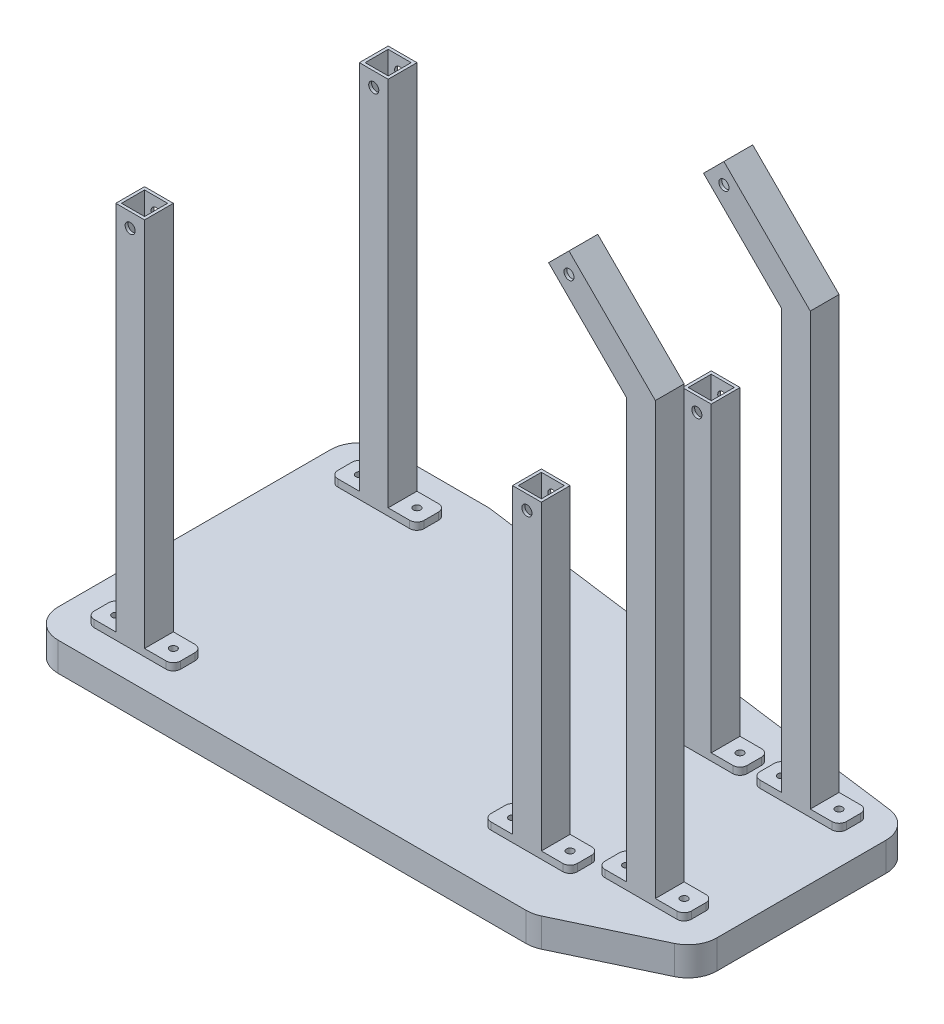
SolidWorks part; units mm, degrees
note: The reader was unsure of these and kept them because the rebuilt part matched: shared geometry of "Sketch4<3>".
ref_plane "Front Plane" through (0, 0, 0) normal (0, 0, 1) x (1, 0, 0)
ref_plane "Top Plane" through (0, 0, 0) normal (0, 1, 0) x (1, 0, 0)
ref_plane "Right Plane" through (0, 0, 0) normal (1, 0, 0) x (0, 0, -1)
sketch "Sketch3" plane through (0, 0, 0) normal (0, 0, 1) x (1, 0, 0)
  line L1 (-396.8516, 25.4) -> (358.309, 25.4) construction
  line L2 (-358.4449, 31.75) -> (285.9975, 31.75) construction
  circle A0 centre (0, 285.496) radius 4.445
  circle A2 centre (23.114, 470.408) radius 4.445
  circle A3 centre (-329.692, 346.456) radius 4.445
  dimension "D6" = 8.89
  dimension "D1" = 23.114
  dimension "D2" = 184.912
  dimension "D3" = 329.692
  dimension "D4" = 60.96
  dimension "D5" = 470.408
  dimension "D7" = 25.4
  dimension "D8" = 6.35
ref_plane "Plane5" through (0, 31.75, 0) normal (0, 1, 0) x (1, 0, 0)
sketch "Sketch4" plane through (0, 31.75, 0) normal (0, 1, 0) x (1, 0, 0)
  line L0 (-329.692, 0) -> (-329.692, 255.8081) construction
  line L1 (0, 0) -> (0, 335.4262) construction
  line L3 (-12.7, 25.4) -> (12.7, 25.4)
  line L4 (-12.7, 25.4) -> (-12.7, 0)
  line L5 (-12.7, 0) -> (12.7, 0)
  line L6 (12.7, 25.4) -> (12.7, 0)
  line L7 (-12.7, 25.4) -> (12.7, 0) construction
  line L8 (-12.7, 0) -> (12.7, 25.4) construction
  line L9 (-12.7, 175.26) -> (12.7, 175.26)
  line L10 (-12.7, 175.26) -> (-12.7, 149.86)
  line L11 (-12.7, 149.86) -> (12.7, 149.86)
  line L12 (12.7, 175.26) -> (12.7, 149.86)
  line L13 (-12.7, 175.26) -> (12.7, 149.86) construction
  line L14 (-12.7, 149.86) -> (12.7, 175.26) construction
  line L15 (-342.392, 5.08) -> (-316.992, 5.08)
  line L16 (-342.392, 5.08) -> (-342.392, -20.32)
  line L17 (-342.392, -20.32) -> (-316.992, -20.32)
  line L18 (-316.992, 5.08) -> (-316.992, -20.32)
  line L19 (-342.392, 5.08) -> (-316.992, -20.32) construction
  line L20 (-342.392, -20.32) -> (-316.992, 5.08) construction
  line L21 (-342.392, 219.964) -> (-316.992, 219.964)
  line L22 (-342.392, 219.964) -> (-342.392, 194.564)
  line L23 (-342.392, 194.564) -> (-316.992, 194.564)
  line L24 (-316.992, 219.964) -> (-316.992, 194.564)
  line L25 (-342.392, 219.964) -> (-316.992, 194.564) construction
  line L26 (-342.392, 194.564) -> (-316.992, 219.964) construction
  point P2 (0, 162.56)
  point P5 (0, 12.7)
  point P16 (-329.692, -7.62)
  point P22 (-329.692, 207.264)
  dimension "D1" = 25.4
  dimension "D2" = 149.86
  dimension "D3" = 20.32
  dimension "D4" = 214.884
extrude "Extrude-Thin1" add sketch "Sketch4" along normal blind 12.7 and the other way up to surface from vertex thin contours L6 L5 L4 L3 | L12 L11 L10 L9 other way up to plane "Plane5" starting at point (0, 285.496, 0) thin type one direction reverse wall 2.54
extrude "Extrude-Thin2" add sketch "Sketch4<3>" along normal blind 12.7 and the other way up to surface from vertex separate body thin contours L15 L18 L17 L16 | L24 L23 L22 L21 other way up to plane "Plane5" starting at point (-329.692, 346.456, 0) thin type one direction reverse wall 2.54
sketch "Sketch4<3>" plane through (0, 31.75, 0) normal (0, 1, 0) x (1, 0, 0) same geometry as "Sketch4"
extrude "Cut-Extrude1" cut sketch "Sketch3" against normal through all both and the other way through all
ref_plane "Plane6" through (0, 0, -39.37) normal (0, 0, 1) x (1, 0, 0)
sketch "Sketch5" plane through (0, 0, -39.37) normal (0, 0, 1) x (1, 0, 0)
  line L0 (23.114, 470.408) -> (86.614, 406.908) construction
  line L1 (86.614, 406.908) -> (86.614, 31.75) construction
  line L2 (-358.4449, 31.75) -> (285.9975, 31.75) construction
  line L3 (5.1535, 470.408) -> (73.914, 401.6475)
  line L4 (23.114, 488.3685) -> (99.314, 412.1685)
  line L5 (73.914, 401.6475) -> (73.914, 31.75)
  line L6 (99.314, 412.1685) -> (99.314, 31.75)
  line L7 (32.0943, 479.3883) -> (95.5943, 415.8883) construction
  line L8 (99.314, 406.908) -> (99.314, 31.75) construction
  line L9 (23.114, 470.408) -> (14.1337, 479.3883) construction
  line L10 (73.914, 406.908) -> (73.914, 31.75) construction
  line L11 (14.1337, 461.4277) -> (77.6337, 397.9277) construction
  line L12 (73.914, 31.75) -> (99.314, 31.75)
  line L13 (5.1535, 470.408) -> (23.114, 488.3685)
  circle A0 centre (23.114, 470.408) radius 4.445 construction
  circle A1 centre (23.114, 470.408) radius 4.445
  dimension "D1" = 135
  dimension "D2" = 63.5
  dimension "D7" = 12.7
  dimension "D3" = 12.7
  dimension "D4" = 12.7
  dimension "D5" = 12.7
  dimension "D6" = 12.7
extrude "Boss-Extrude1" add sketch "Sketch5" along normal blind 25.4 separate body
sketch "Sketch6" plane through (0, 0, -39.37) normal (0, 0, -1) x (-1, 0, 0)
  line L0 (-86.614, 406.908) -> (-86.614, 31.75) construction
  line L1 (-23.114, 470.408) -> (-14.1337, 479.3883) construction
  line L2 (-23.114, 470.408) -> (-86.614, 406.908) construction
  line L3 (-86.614, 406.908) -> (-86.614, 31.75) construction
  line L4 (-23.114, 470.408) -> (-14.1337, 479.3883) construction
  line L5 (-23.114, 470.408) -> (-86.614, 406.908) construction
  line L6 (-76.454, 402.6996) -> (-76.454, 31.75)
  line L7 (-15.9298, 463.2238) -> (-76.454, 402.6996)
  line L8 (-15.9298, 463.2238) -> (-6.9495, 472.2041)
  line L9 (-96.774, 411.1164) -> (-96.774, 31.75)
  line L10 (-30.2982, 477.5922) -> (-96.774, 411.1164)
  line L11 (-30.2982, 477.5922) -> (-21.3179, 486.5725)
  line L12 (-21.3179, 486.5725) -> (-6.9495, 472.2041)
  line L13 (-96.774, 31.75) -> (-76.454, 31.75)
  dimension "D1" = 10.16
  dimension "D2" = 10.16
extrude "Cut-Extrude2" cut sketch "Sketch6" against normal blind 20.32 from offset 2.54 offset against normal yes
ref_plane "Plane7" through (0, 0, -150.622) normal (0, 0, -1) x (-1, 0, 0)
ref_plane "Plane8" through (0, 0, -94.996) normal (0, 0, -1) x (-1, 0, 0)
mirror "Mirror1" about plane through (0, 0, -94.996) normal (0, 0, -1) of bodies 135
sketch "Sketch7" plane through (0, 31.75, 0) normal (0, -1, 0) x (1, 0, 0)
  line L0 (-342.392, -5.08) -> (-316.992, 20.32) construction
  line L1 (-342.392, -219.964) -> (-316.992, -194.564) construction
  line L2 (12.7, 0) -> (-12.7, -25.4) construction
  line L3 (-316.992, 20.32) -> (-342.392, 20.32) construction
  line L4 (-361.442, 20.32) -> (-297.942, 20.32)
  line L5 (-367.792, 13.97) -> (-367.792, 1.27)
  line L6 (-361.442, -5.08) -> (-297.942, -5.08)
  line L7 (-291.592, 13.97) -> (-291.592, 1.27)
  line L8 (-367.792, 20.32) -> (-291.592, -5.08) construction
  line L9 (-367.792, -5.08) -> (-291.592, 20.32) construction
  line L10 (-342.392, 7.62) -> (-367.792, 7.62) construction
  line L11 (-342.392, 20.32) -> (-342.392, -5.08) construction
  line L12 (-316.992, 7.62) -> (-291.592, 7.62) construction
  line L13 (-316.992, 20.32) -> (-316.992, -5.08) construction
  line L14 (-329.692, 7.62) -> (-329.692, -207.264) construction
  line L15 (-329.692, -99.822) -> (-371.4791, -99.822) construction
  line L16 (-316.992, -207.264) -> (-291.592, -207.264) construction
  line L17 (-342.392, -207.264) -> (-367.792, -207.264) construction
  line L18 (-367.792, -194.564) -> (-291.592, -219.964) construction
  line L19 (-367.792, -219.964) -> (-291.592, -194.564) construction
  line L20 (-342.392, -194.564) -> (-316.992, -219.964) construction
  line L21 (-291.592, -213.614) -> (-291.592, -200.914)
  line L22 (-361.442, -194.564) -> (-297.942, -194.564)
  line L23 (-367.792, -213.614) -> (-367.792, -200.914)
  line L24 (-361.442, -219.964) -> (-297.942, -219.964)
  line L25 (12.7, 0) -> (-12.7, 0) construction
  line L26 (-31.75, 0) -> (31.75, 0)
  line L27 (-38.1, -6.35) -> (-38.1, -19.05)
  line L28 (-31.75, -25.4) -> (31.75, -25.4)
  line L29 (38.1, -6.35) -> (38.1, -19.05)
  line L30 (-38.1, 0) -> (38.1, -25.4) construction
  line L31 (-38.1, -25.4) -> (38.1, 0) construction
  line L32 (-12.7, -12.7) -> (-38.1, -12.7) construction
  line L33 (-12.7, 0) -> (-12.7, -25.4) construction
  line L34 (12.7, -12.7) -> (38.1, -12.7) construction
  line L35 (12.7, 0) -> (12.7, -25.4) construction
  line L36 (-12.7, -175.26) -> (12.7, -149.86) construction
  line L37 (0, -12.7) -> (0, -162.56) construction
  line L38 (0, -87.63) -> (-50.2547, -87.63) construction
  line L39 (12.7, -162.56) -> (38.1, -162.56) construction
  line L40 (-12.7, -162.56) -> (-38.1, -162.56) construction
  line L41 (-38.1, -149.86) -> (38.1, -175.26) construction
  line L42 (-38.1, -175.26) -> (38.1, -149.86) construction
  line L43 (12.7, -175.26) -> (-12.7, -149.86) construction
  line L44 (38.1, -168.91) -> (38.1, -156.21)
  line L45 (-31.75, -149.86) -> (31.75, -149.86)
  line L46 (-38.1, -168.91) -> (-38.1, -156.21)
  line L47 (-31.75, -175.26) -> (31.75, -175.26)
  line L48 (99.314, -13.97) -> (73.914, -39.37) construction
  line L49 (73.914, -176.022) -> (99.314, -150.622) construction
  line L50 (73.914, -13.97) -> (99.314, -13.97) construction
  line L51 (54.864, -13.97) -> (118.364, -13.97)
  line L52 (48.514, -20.32) -> (48.514, -33.02)
  line L53 (54.864, -39.37) -> (118.364, -39.37)
  line L54 (124.714, -20.32) -> (124.714, -33.02)
  line L55 (48.514, -13.97) -> (124.714, -39.37) construction
  line L56 (48.514, -39.37) -> (124.714, -13.97) construction
  line L57 (73.914, -26.67) -> (48.514, -26.67) construction
  line L58 (73.914, -13.97) -> (73.914, -39.37) construction
  line L59 (99.314, -26.67) -> (124.714, -26.67) construction
  line L60 (99.314, -13.97) -> (99.314, -39.37) construction
  line L61 (86.614, -26.67) -> (86.614, -163.322) construction
  line L62 (86.614, -94.996) -> (61.214, -94.996) construction
  line L63 (-51.7883, -94.996) -> (51.7883, -94.996) construction
  line L64 (99.314, -163.322) -> (124.714, -163.322) construction
  line L65 (73.914, -163.322) -> (48.514, -163.322) construction
  line L66 (48.514, -150.622) -> (124.714, -176.022) construction
  line L67 (48.514, -176.022) -> (124.714, -150.622) construction
  line L68 (99.314, -176.022) -> (73.914, -150.622) construction
  line L69 (124.714, -169.672) -> (124.714, -156.972)
  line L70 (54.864, -150.622) -> (118.364, -150.622)
  line L71 (48.514, -169.672) -> (48.514, -156.972)
  line L72 (54.864, -176.022) -> (118.364, -176.022)
  circle A0 centre (-355.092, 7.62) radius 3.175
  circle A1 centre (-304.292, 7.62) radius 3.175
  arc A2 (-297.942, 20.32) -> (-291.592, 13.97) centre (-297.942, 13.97) cw
  arc A3 (-297.942, -5.08) -> (-291.592, 1.27) centre (-297.942, 1.27) ccw
  arc A4 (-367.792, 1.27) -> (-361.442, -5.08) centre (-361.442, 1.27) ccw
  arc A5 (-361.442, 20.32) -> (-367.792, 13.97) centre (-361.442, 13.97) ccw
  arc A6 (-361.442, -219.964) -> (-367.792, -213.614) centre (-361.442, -213.614) cw
  arc A7 (-367.792, -200.914) -> (-361.442, -194.564) centre (-361.442, -200.914) cw
  arc A8 (-297.942, -194.564) -> (-291.592, -200.914) centre (-297.942, -200.914) cw
  arc A9 (-297.942, -219.964) -> (-291.592, -213.614) centre (-297.942, -213.614) ccw
  circle A10 centre (-304.292, -207.264) radius 3.175
  circle A11 centre (-355.092, -207.264) radius 3.175
  circle A12 centre (-25.4, -12.7) radius 3.175
  circle A13 centre (25.4, -12.7) radius 3.175
  arc A14 (31.75, -25.4) -> (38.1, -19.05) centre (31.75, -19.05) ccw
  arc A15 (31.75, 0) -> (38.1, -6.35) centre (31.75, -6.35) cw
  arc A16 (-38.1, -19.05) -> (-31.75, -25.4) centre (-31.75, -19.05) ccw
  arc A17 (-31.75, 0) -> (-38.1, -6.35) centre (-31.75, -6.35) ccw
  arc A18 (-31.75, -175.26) -> (-38.1, -168.91) centre (-31.75, -168.91) cw
  arc A19 (-38.1, -156.21) -> (-31.75, -149.86) centre (-31.75, -156.21) cw
  arc A20 (31.75, -175.26) -> (38.1, -168.91) centre (31.75, -168.91) ccw
  arc A21 (31.75, -149.86) -> (38.1, -156.21) centre (31.75, -156.21) cw
  circle A22 centre (25.4, -162.56) radius 3.175
  circle A23 centre (-25.4, -162.56) radius 3.175
  circle A24 centre (61.214, -26.67) radius 3.175
  circle A25 centre (112.014, -26.67) radius 3.175
  arc A26 (118.364, -13.97) -> (124.714, -20.32) centre (118.364, -20.32) cw
  arc A27 (54.864, -13.97) -> (48.514, -20.32) centre (54.864, -20.32) ccw
  arc A28 (118.364, -39.37) -> (124.714, -33.02) centre (118.364, -33.02) ccw
  arc A29 (48.514, -33.02) -> (54.864, -39.37) centre (54.864, -33.02) ccw
  arc A30 (48.514, -156.972) -> (54.864, -150.622) centre (54.864, -156.972) cw
  arc A31 (118.364, -150.622) -> (124.714, -156.972) centre (118.364, -156.972) cw
  arc A32 (54.864, -176.022) -> (48.514, -169.672) centre (54.864, -169.672) cw
  arc A33 (118.364, -176.022) -> (124.714, -169.672) centre (118.364, -169.672) ccw
  circle A34 centre (112.014, -163.322) radius 3.175
  circle A35 centre (61.214, -163.322) radius 3.175
  point P12 (-329.692, 7.62)
  point P73 (-329.692, -207.264)
  point P74 (0, -12.7)
  point P139 (0, -162.56)
  point P148 (86.614, -26.67)
  point P211 (86.614, -163.322)
  dimension "D2" = 6.35
  dimension "D3" = 6.35
  dimension "D5" = 6.35
  dimension "D6" = 6.35
  dimension "D8" = 6.35
  dimension "D9" = 6.35
  dimension "D1" = 76.2
  dimension "D4" = 76.2
  dimension "D7" = 76.2
extrude "Boss-Extrude2" add sketch "Sketch7" along normal blind 6.35
sketch "Sketch8" plane through (0, 25.4, 0) normal (0, -1, 0) x (1, 0, 0)
  line L0 (-367.792, 45.72) -> (45.0943, 45.72)
  line L1 (55.9576, 43.2797) -> (135.5773, 5.608)
  line L2 (150.114, -17.3517) -> (150.114, -166.4552)
  line L3 (128.0387, -191.6366) -> (-277.2368, -245.1455)
  line L4 (-280.5615, -245.364) -> (-367.792, -245.364)
  line L5 (-393.192, -219.964) -> (-393.192, 20.32)
  line L6 (-367.792, 13.97) -> (-367.792, 1.27) construction
  line L7 (-297.942, 20.32) -> (-361.442, 20.32) construction
  line L8 (-361.442, -219.964) -> (-297.942, -219.964) construction
  line L9 (124.714, -33.02) -> (124.714, -20.32) construction
  line L10 (-291.592, -213.614) -> (-291.592, -219.964) construction
  line L11 (31.75, 0) -> (38.1, 0) construction
  line L12 (38.1, 0) -> (38.1, -6.35) construction
  line L13 (118.364, -13.97) -> (124.714, -13.97) construction
  line L14 (124.714, -13.97) -> (124.714, -20.32) construction
  line L15 (124.714, -169.672) -> (124.714, -176.022) construction
  line L16 (124.714, -176.022) -> (118.364, -176.022) construction
  line L17 (-291.592, -219.964) -> (-297.942, -219.964) construction
  arc A0 (45.0943, 45.72) -> (55.9576, 43.2797) centre (45.0943, 20.32) cw
  arc A1 (135.5773, 5.608) -> (150.114, -17.3517) centre (124.714, -17.3517) cw
  arc A2 (150.114, -166.4552) -> (128.0387, -191.6366) centre (124.714, -166.4552) cw
  arc A3 (-277.2368, -245.1455) -> (-280.5615, -245.364) centre (-280.5615, -219.964) cw
  arc A4 (-367.792, -245.364) -> (-393.192, -219.964) centre (-367.792, -219.964) cw
  arc A5 (-367.792, 45.72) -> (-393.192, 20.32) centre (-367.792, 20.32) ccw
  point P33 (54.9604, 45.72)
  point P38 (50.8, 45.72)
  point P41 (150.114, -1.27)
  point P44 (150.114, -188.722)
  point P47 (-278.892, -245.364)
  dimension "D9" = 25.4
  dimension "D1" = 25.4
  dimension "D2" = 25.4
  dimension "D3" = 25.4
  dimension "D4" = 25.4
  dimension "D5" = 12.7
  dimension "D6" = 12.7
  dimension "D7" = 12.7
  dimension "D8" = 12.7
extrude "Boss-Extrude3" add sketch "Sketch8" along normal blind 25.4 separate body
sketch "Sketch9" plane through (0, 25.4, 0) normal (0, 1, 0) x (1, 0, 0)
  circle A0 centre (-355.092, 207.264) radius 3.175 construction
  circle A1 centre (-355.092, 207.264) radius 3.175
  circle A2 centre (-304.292, 207.264) radius 3.175 construction
  circle A3 centre (-304.292, 207.264) radius 3.175
  circle A4 centre (-25.4, 162.56) radius 3.175 construction
  circle A5 centre (-25.4, 162.56) radius 3.175
  circle A6 centre (112.014, 163.322) radius 3.175 construction
  circle A7 centre (112.014, 163.322) radius 3.175
  circle A8 centre (25.4, 162.56) radius 3.175 construction
  circle A9 centre (25.4, 162.56) radius 3.175
  circle A10 centre (61.214, 163.322) radius 3.175 construction
  circle A11 centre (61.214, 163.322) radius 3.175
  circle A12 centre (-25.4, 12.7) radius 3.175 construction
  circle A13 centre (-25.4, 12.7) radius 3.175
  circle A14 centre (25.4, 12.7) radius 3.175 construction
  circle A15 centre (25.4, 12.7) radius 3.175
  circle A16 centre (61.214, 26.67) radius 3.175 construction
  circle A17 centre (61.214, 26.67) radius 3.175
  circle A18 centre (112.014, 26.67) radius 3.175 construction
  circle A19 centre (112.014, 26.67) radius 3.175
  circle A20 centre (-355.092, -7.62) radius 3.175 construction
  circle A21 centre (-355.092, -7.62) radius 3.175
  circle A22 centre (-304.292, -7.62) radius 3.175 construction
  circle A23 centre (-304.292, -7.62) radius 3.175
extrude "Cut-Extrude3" cut sketch "Sketch9" against normal through all both and the other way through all
